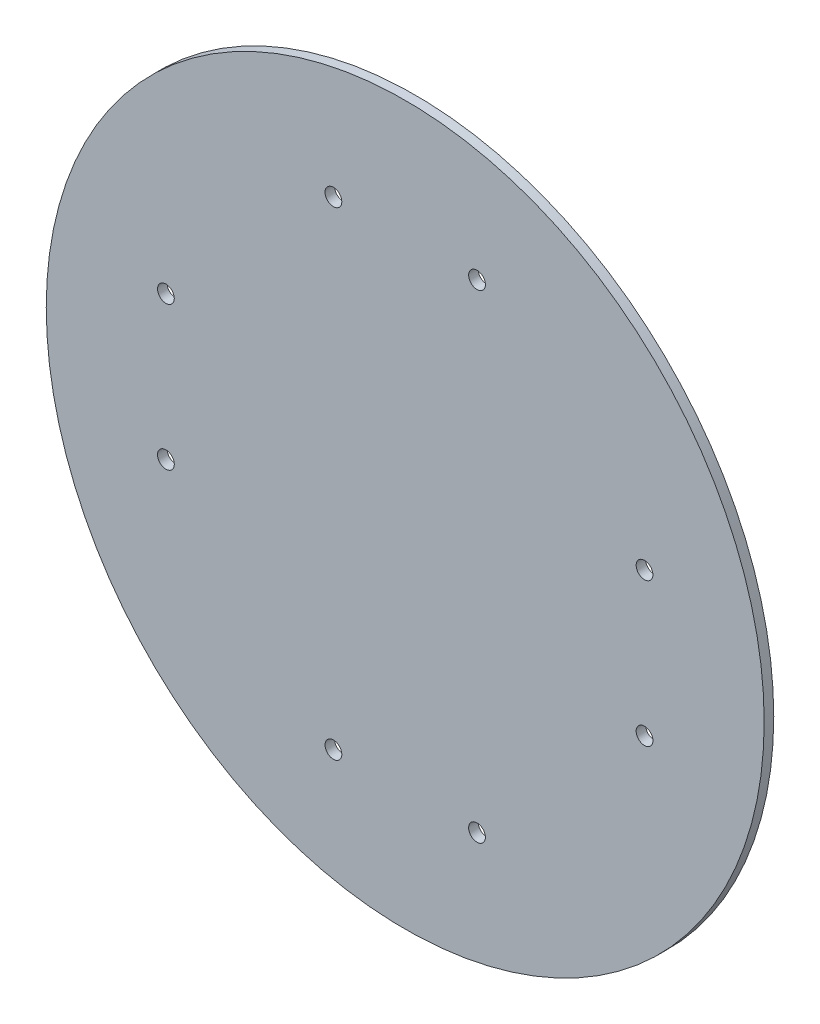
SolidWorks part; units mm, degrees
ref_plane "Front Plane" through (0, 0, 0) normal (0, 0, 1) x (1, 0, 0)
ref_plane "Top Plane" through (0, 0, 0) normal (0, 1, 0) x (1, 0, 0)
ref_plane "Right Plane" through (0, 0, 0) normal (1, 0, 0) x (0, 0, -1)
sketch "Sketch1" plane through (0, 0, 0) normal (0, 0, 1) x (1, 0, 0)
  circle A0 centre (0, 0) radius 75
  dimension "D1" = 150
extrude "Boss-Extrude1" add sketch "Sketch1" along normal blind 2
sketch "Sketch2" plane through (0, 0, 0) normal (0, 0, -1) x (-1, 0, 0)
  line L1 (-50, 15) -> (50, 15) construction
  line L2 (-50, 15) -> (-50, -15) construction
  line L3 (-50, -15) -> (50, -15) construction
  line L4 (50, 15) -> (50, -15) construction
  line L5 (-50, 15) -> (50, -15) construction
  line L6 (-50, -15) -> (50, 15) construction
  line L7 (-15, 50) -> (15, 50) construction
  line L8 (-15, 50) -> (-15, -50) construction
  line L9 (-15, -50) -> (15, -50) construction
  line L10 (15, 50) -> (15, -50) construction
  line L11 (-15, 50) -> (15, -50) construction
  line L12 (-15, -50) -> (15, 50) construction
  circle A0 centre (-50, 15) radius 1.75
  circle A1 centre (-50, -15) radius 1.75
  circle A2 centre (-15, -50) radius 1.75
  circle A3 centre (15, -50) radius 1.75
  circle A4 centre (50, -15) radius 1.75
  circle A5 centre (50, 15) radius 1.75
  circle A6 centre (-15, 50) radius 1.75
  circle A7 centre (15, 50) radius 1.75
  point P0 (0, 0)
  point P6 (0, 0)
  dimension "D3" = 3.5
  dimension "D1" = 100
  dimension "D2" = 30
extrude "Cut-Extrude1" cut sketch "Sketch2" against normal through all
